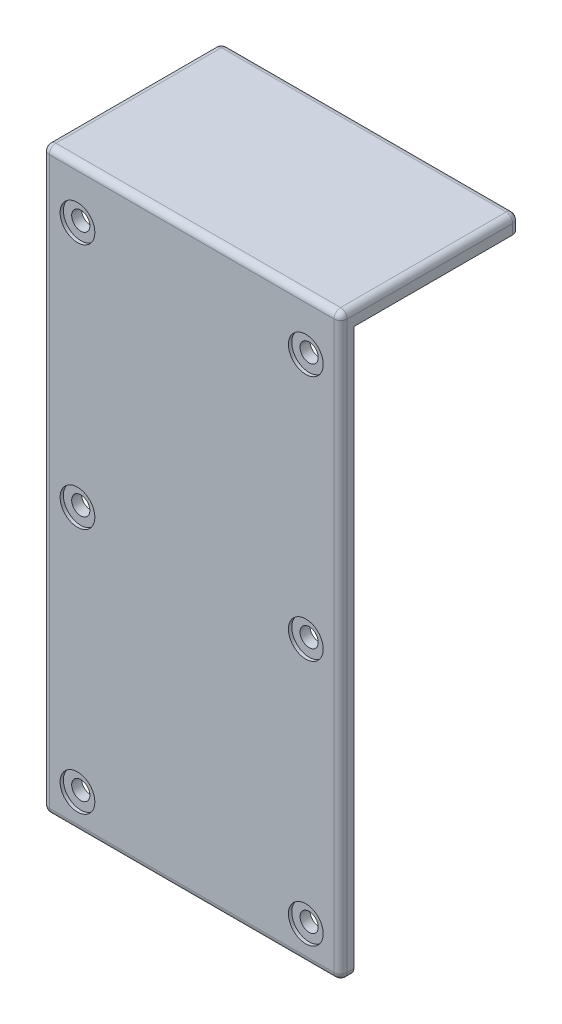
SolidWorks part; units mm, degrees
ref_plane "Front Plane" through (0, 0, 0) normal (0, 0, 1) x (1, 0, 0)
ref_plane "Top Plane" through (0, 0, 0) normal (0, 1, 0) x (1, 0, 0)
ref_plane "Right Plane" through (0, 0, 0) normal (1, 0, 0) x (0, 0, -1)
sketch "Sketch1" plane through (0, 0, 0) normal (0, 0, 1) x (1, 0, 0)
  line L1 (0, 0) -> (90, 0)
  line L2 (0, 0) -> (0, 170)
  line L3 (0, 170) -> (90, 170)
  line L4 (90, 0) -> (90, 170)
  dimension "D1" = 90
  dimension "D2" = 170
extrude "Boss-Extrude1" add sketch "Sketch1" along normal blind 4
sketch "Sketch2" plane through (0, 0, 4) normal (0, 0, 1) x (1, 0, 0)
  line L0 (10.5, 159.5) -> (10.5, 10.5) construction
  line L3 (0, 170) -> (10.5, 170) construction
  line L4 (0, 170) -> (0, 159.5) construction
  line L5 (0, 159.5) -> (10.5, 159.5) construction
  line L7 (10.5, 170) -> (10.5, 159.5) construction
  line L8 (90, 170) -> (79.5, 170) construction
  line L9 (90, 170) -> (90, 159.5) construction
  line L11 (90, 159.5) -> (79.5, 159.5) construction
  line L12 (79.5, 170) -> (79.5, 159.5) construction
  line L13 (0, 0) -> (10.5, 0) construction
  line L14 (0, 0) -> (0, 10.5) construction
  line L15 (0, 10.5) -> (10.5, 10.5) construction
  line L16 (10.5, 0) -> (10.5, 10.5) construction
  line L17 (90, 0) -> (79.5, 0) construction
  line L18 (90, 0) -> (90, 10.5) construction
  line L19 (90, 10.5) -> (79.5, 10.5) construction
  line L20 (79.5, 0) -> (79.5, 10.5) construction
  line L21 (79.5, 159.5) -> (79.5, 10.5) construction
  point P16 (10.5, 85)
  point P17 (10.5, 159.5)
  point P18 (79.5, 85)
  point P19 (10.5, 10.5)
  point P20 (79.5, 10.5)
  point P22 (79.5, 159.5)
  dimension "D1" = 69
hole_wizard "CBORE for M5 SBHCS1" positions "Sketch2" profile "Sketch3" counterbore size "M5" standard "ANSI Metric" end condition through all
sketch "Sketch3" plane through (79.5, 159.5, 4) normal (1, 0, 0) x (0, -1, 0)
  line L0 (0, 0) -> (0, 4)
  line L1 (0, 4) -> (2.75, 4)
  line L3 (2.75, 4) -> (2.75, 1)
  line L4 (2.75, 1) -> (5.25, 1)
  line L5 (5.25, 1) -> (5.25, 0)
  line L7 (5.25, 0) -> (0, 0)
  line L11 (0, -6.35) -> (0, 107.95) construction
  dimension "Thru Hole Dia." = 5.5
  dimension "Thru Hole Depth" = 4
  dimension "C'Bore Dia." = 10.5
  dimension "C'Bore Depth" = 1
sketch "Sketch4" plane through (0, 170, 0) normal (0, 1, 0) x (1, 0, 0)
  line L1 (0, -4) -> (90, -4)
  line L2 (0, -4) -> (0, 50)
  line L3 (0, 50) -> (90, 50)
  line L4 (90, -4) -> (90, 50)
  point P5 (90, -4)
  dimension "D1" = 54
extrude "Boss-Extrude2" add sketch "Sketch4" along normal blind 5
fillet "Fillet1" radius 2 11 edges at (0, 172.5, -50) (90, 172.5, -50) (45, 175, -50) (90, 0, 2) (0, 0, 2) (45, 0, 4) (0, 87.5, 4) (0, 175, -23) (90, 175, -23) (90, 87.5, 4) (45, 175, 4)
